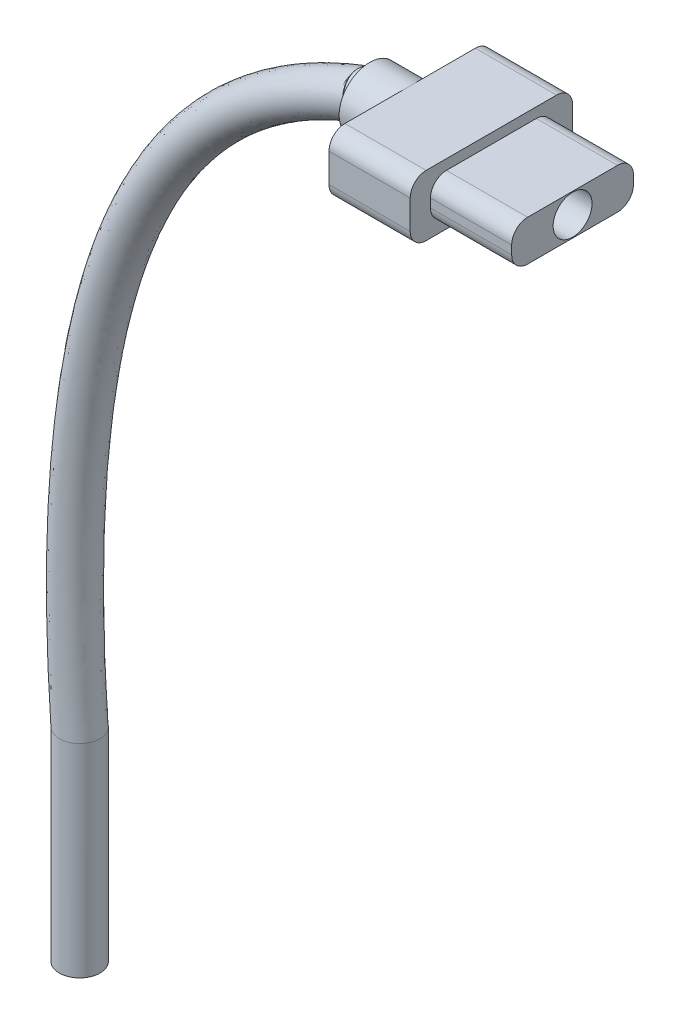
SolidWorks part; units mm, degrees
ref_plane "Front Plane" through (0, 0, 0) normal (0, 0, 1) x (1, 0, 0)
ref_plane "Top Plane" through (0, 0, 0) normal (0, 1, 0) x (1, 0, 0)
ref_plane "Right Plane" through (0, 0, 0) normal (1, 0, 0) x (0, 0, -1)
sketch "Sketch1" plane through (0, 0, 0) normal (0, 0, 1) x (1, 0, 0)
  line L0 (0, 0) -> (27.94, 0) construction
  line L1 (27.94, 0) -> (27.94, 45.212) construction
  line L2 (17.78, 0) -> (17.78, 43.18) construction
  line L3 (22.86, 0) -> (22.86, 44.5939) construction
  spline S0 degree 2 poles (0, 0) (-2.5721, 35.5119) (17.78, 43.18) knots 0 0 0 0.818411 0.818411 0.818411
  dimension "D1" = 27.94
  dimension "D2" = 45.212
  dimension "D3" = 43.18
  dimension "D4" = 10.16
  dimension "D5" = 5.08
sketch "Sketch2" plane through (0, 0, 0) normal (0, 1, 0) x (1, 0, 0)
  circle A0 centre (0, 0) radius 1.27
  dimension "D1" = 2.54
sweep "Sweep1" add profiles "Sketch2" path "Sketch1"
sketch "Sketch3" plane through (0, 0, 0) normal (0, -1, 0) x (1, 0, 0)
  circle A1 centre (0, 0) radius 1.27
  circle A2 centre (0, 0) radius 1.27
  dimension "D1" = 0
extrude "Boss-Extrude1" add sketch "Sketch3" along normal blind 12.7
sketch "Sketch5" plane through (0, 0, 0) normal (0, 0, 1) x (1, 0, 0)
  line L0 (18.1407, 41.9623) -> (17.4193, 44.3977) construction
  line L1 (18.1407, 41.9623) -> (17.4193, 44.3977)
  line L2 (17.4193, 44.3977) -> (18.1407, 44.3977)
  line L3 (18.1407, 44.3977) -> (18.1407, 41.9623)
  line L4 (18.1407, 43.18) -> (17.78, 43.18)
  line L5 (17.78, 43.18) -> (24.2705, 43.18)
revolve "Revolve1" add sketch "Sketch5" angle 360 about L5 region at (17.8602, 43.8565, 0)
sketch "Sketch6" plane through (18.1407, 0, 0) normal (1, 0, 0) x (0, 0, -1)
  circle A0 centre (0, 43.18) radius 1.905
  circle A1 centre (0, 43.18) radius 1.2177
  circle A2 centre (0, 43.18) radius 1.2177
  dimension "D2" = 3.81
  dimension "D1" = 0
extrude "Boss-Extrude2" add sketch "Sketch6" along normal blind 2.54 separate body
sketch "Sketch7" plane through (20.6807, 0, 0) normal (1, 0, 0) x (0, 0, -1)
  line L1 (-5.08, 45.085) -> (5.08, 45.085)
  line L2 (-5.08, 45.085) -> (-5.08, 41.275)
  line L3 (-5.08, 41.275) -> (5.08, 41.275)
  line L4 (5.08, 45.085) -> (5.08, 41.275)
  line L5 (-5.08, 45.085) -> (5.08, 41.275) construction
  line L6 (-5.08, 41.275) -> (5.08, 45.085) construction
  circle A1 centre (0, 43.18) radius 1.2177
  circle A2 centre (0, 43.18) radius 1.2177
  dimension "D2" = 3.81
  dimension "D3" = 10.16
  dimension "D1" = 0
extrude "Boss-Extrude3" add sketch "Sketch7" along normal blind 5.08
sketch "Sketch8" plane through (25.7607, 0, 0) normal (1, 0, 0) x (0, 0, -1)
  line L1 (-3.81, 44.45) -> (3.81, 44.45)
  line L2 (-3.81, 44.45) -> (-3.81, 41.91)
  line L3 (-3.81, 41.91) -> (3.81, 41.91)
  line L4 (3.81, 44.45) -> (3.81, 41.91)
  line L5 (-3.81, 44.45) -> (3.81, 41.91) construction
  line L6 (-3.81, 41.91) -> (3.81, 44.45) construction
  circle A1 centre (0, 43.18) radius 1.2177
  circle A2 centre (0, 43.18) radius 1.2177
  dimension "D2" = 7.62
  dimension "D3" = 2.54
  dimension "D1" = 0
extrude "Boss-Extrude4" add sketch "Sketch8" along normal blind 5.08 separate body
fillet "Fillet1" radius 1 4 edges at (23.2207, 41.275, -5.08) (23.2207, 45.085, -5.08) (23.2207, 41.275, 5.08) (23.2207, 45.085, 5.08)
fillet "Fillet2" radius 1 4 edges at (28.3007, 41.91, 3.81) (28.3007, 41.91, -3.81) (28.3007, 44.45, 3.81) (28.3007, 44.45, -3.81)
equation "\"`\"=0.1"
